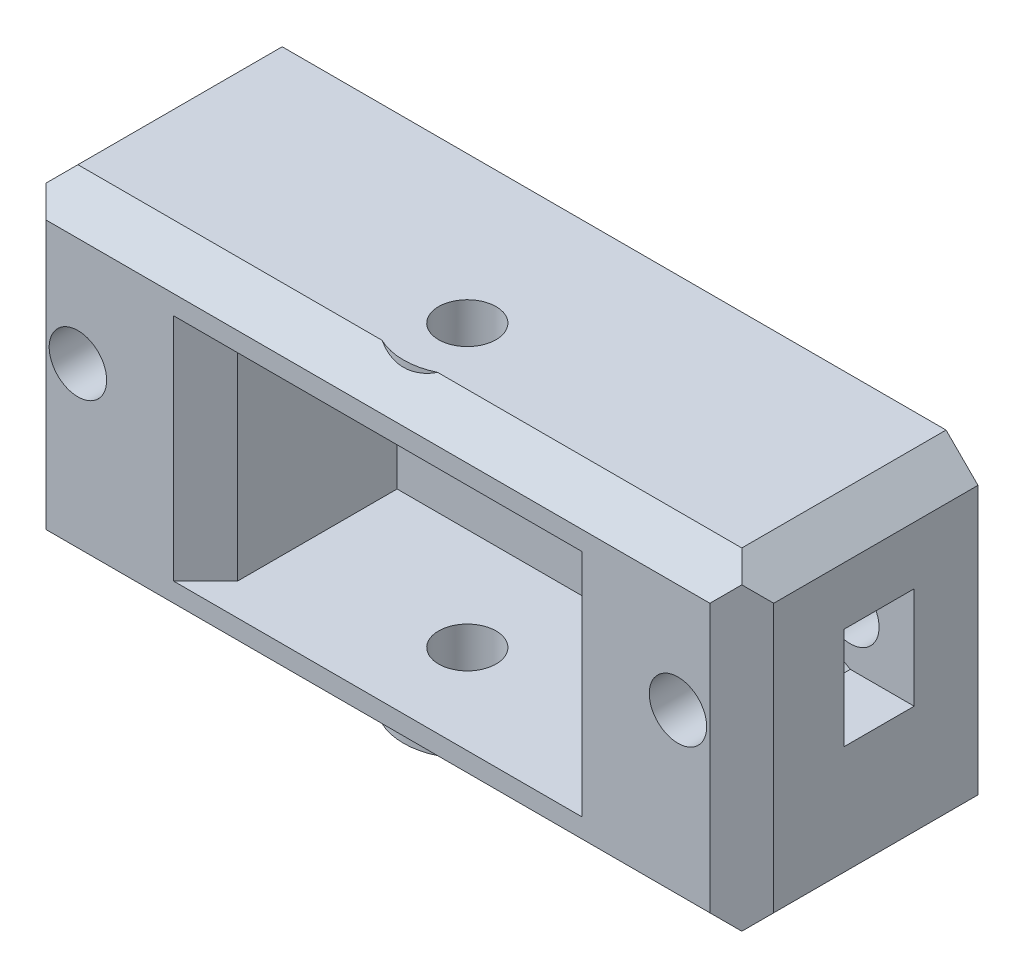
SolidWorks part; units mm, degrees
ref_plane "Plan de face" through (0, 0, 0) normal (0, 0, 1) x (1, 0, 0)
ref_plane "Plan de dessus" through (0, 0, 0) normal (0, 1, 0) x (1, 0, 0)
ref_plane "Plan de droite" through (0, 0, 0) normal (1, 0, 0) x (0, 0, -1)
sketch "Esquisse1" plane through (0, 0, 0) normal (0, 0, 1) x (1, 0, 0)
  line L1 (0, 0) -> (57, 0)
  line L2 (0, 0) -> (0, -26)
  line L3 (0, -26) -> (57, -26)
  line L4 (57, 0) -> (57, -26)
  line L5 (37.5, -6) -> (32, -6)
  line L6 (37.5, -6) -> (37.5, -16)
  line L7 (37.5, -16) -> (32, -16)
  line L8 (32, -6) -> (32, -16)
  line L9 (25, -6) -> (19.5, -6)
  line L10 (25, -6) -> (25, -16)
  line L11 (25, -16) -> (19.5, -16)
  line L12 (19.5, -6) -> (19.5, -16)
  circle A0 centre (5, -11) radius 2.25
  circle A1 centre (52, -11) radius 2.25
  point P17 (34.75, -6)
  point P18 (28.5, 0)
  dimension "D3" = 4.5
  dimension "D4" = 4.5
  dimension "D7" = 11
  dimension "D1" = 26
  dimension "D2" = 57
  dimension "D5" = 5
  dimension "D6" = 5
  dimension "D8" = 11
  dimension "D9" = 5.5
  dimension "D10" = 5.5
  dimension "D11" = 10
  dimension "D12" = 10
  dimension "D13" = 6
  dimension "D14" = 6
  dimension "D15" = 3.5
  dimension "D16" = 3.5
extrude "Boss.-Extru.2" add sketch "Esquisse1" along normal blind 3.5
ref_plane "Plan1" through (28.5, 0, 0) normal (1, 0, 0) x (0, 0, -1)
sketch "Esquisse6" plane through (0, 0, 3.5) normal (0, 0, 1) x (1, 0, 0)
  line L0 (15, 0) -> (15, -26)
  line L1 (57, 0) -> (0, 0) construction
  line L2 (0, -26) -> (57, -26) construction
  line L3 (15, -26) -> (42, -26)
  line L4 (42, -26) -> (42, 0)
  line L5 (42, 0) -> (57, 0)
  line L6 (57, 0) -> (57, -26)
  line L7 (57, -26) -> (42, -26)
  line L8 (15, -26) -> (0, -26)
  line L9 (0, -26) -> (0, 0)
  line L10 (0, 0) -> (15, 0)
  line L11 (15, -22) -> (42, -22)
  line L13 (0, 0) -> (57, 0)
  line L14 (0, 0) -> (0, -4)
  line L15 (0, -4) -> (57, -4)
  line L16 (57, 0) -> (57, -4)
  line L17 (0, -4) -> (57, -4)
  line L18 (0, -4) -> (0, 0)
  line L19 (0, 0) -> (57, 0)
  line L20 (57, -4) -> (57, 0)
  circle M9 centre (5, -11) radius 2.25
  line M10 (0, 0) -> (0, -26)
  line M11 (0, -26) -> (57, -26)
  line M12 (57, -26) -> (57, 0)
  line M13 (57, 0) -> (0, 0)
  circle M14 centre (52, -11) radius 2.25
  line M15 (32, -6) -> (37.5, -6)
  line M19 (19.5, -6) -> (25, -6)
  dimension "D1" = 15
  dimension "D2" = 15
  dimension "D3" = 4
  dimension "D4" = 18
  dimension "D5" = 4
  dimension "D6" = 26
extrude "Boss.-Extru.8" add sketch "Esquisse6" along normal blind 15 and the other way up to surface (3.5 mm away) contours L15 L9 L0 M11 M9 | L11 L0 L4 M11 | L15 L4 M11 M12 M14 | L4 L15 L6 M13 | L0 L15 L4 M19 M15 M13 | L15 L0 M10 M13 region at (28.5, -24, 3.5) region at (7.6266, -15.2025, 3.5) region at (7.5, -2, 3.5) region at (28.5, -2, 3.5) region at (49.3734, -15.2025, 3.5) region at (49.5, -2, 3.5) other way up to face at (34.75, -11, 0)
sketch "Esquisse7" plane through (0, 0, 0) normal (0, 1, 0) x (1, 0, 0)
  line L0 (15, -3.5) -> (42, -3.5) construction
  line L1 (28.5, -10.175) -> (28.5, 10.175) construction
  circle A0 centre (28.5, -11.5) radius 2.25
  point P4 (28.5, -3.5)
  dimension "D1" = 4.5
  dimension "D2" = 8
  dimension "D3" = 0
extrude "Enlèv. mat.-Extru.1" cut sketch "Esquisse7" against normal blind 30
sketch "Esquisse8" plane through (0, 0, 0) normal (0, 0, -1) x (-1, 0, 0)
  line L0 (-57, -26) -> (-57, 0) construction
  line L1 (-48.55, -12.9919) -> (-48.55, -9.0081)
  line L2 (-48.55, -9.0081) -> (-52, -7.0163)
  line L3 (-52, -7.0163) -> (-55.45, -9.0081)
  line L4 (-55.45, -9.0081) -> (-55.45, -12.9919)
  line L5 (-55.45, -12.9919) -> (-52, -14.9837)
  line L6 (-52, -14.9837) -> (-48.55, -12.9919)
  line L7 (-52, -7.0163) -> (-57, -7.0163)
  line L8 (-57, -7.0163) -> (-57, -14.9837)
  line L9 (-57, -14.9837) -> (-52, -14.9837)
  circle A0 centre (-52, -11) radius 3.45 construction
  line M7 (-57, 0) -> (-57, -26)
  circle M12 centre (-52, -11) radius 2.25
  dimension "D1" = 180
  dimension "D2" = 6.9
  dimension "D3" = 90
  dimension "D4" = 90
extrude "Enlèv. mat.-Extru.2" cut sketch "Esquisse8" against normal blind 5.5 from offset 5 contours L9 L5 L4 L3 L7 M7 | L5 L6 L1 L2 L3 L4 M12 region at (50.3277, -13.8965, 0) region at (55.5368, -11, 0) offset against normal yes
mirror "Symétrie1" about plane through (28.5, 0, 0) normal (1, 0, 0) of "Enlèv. mat.-Extru.2"
chamfer "Chanfrein2" distance 2.5 angle 45 2 edges at (57, -13, 18.5) (0, -13, 18.5)
chamfer "Chanfrein3" distance 2.5 angle 45 8 edges at (57, -26, 8) (57, 0, 8) (0, 0, 8) (0, -26, 8) (42, -13, 18.5) (15, -13, 18.5) (28.5, -26, 18.5) (28.5, 0, 18.5)
sketch "Esquisse10" plane through (0, 0, 0) normal (0, 1, 0) x (1, 0, 0)
  circle A0 centre (28.5, -11.5) radius 5
  circle A1 centre (28.5, -11.5) radius 2.75
  dimension "D1" = 10
extrude "Boss.-Extru.9" add sketch "Esquisse10" against normal up to next (4 mm away)
ref_plane "Plan2" through (0, -13, 0) normal (0, 1, 0) x (1, 0, 0)
mirror "Symétrie2" about plane through (0, -13, 0) normal (0, 1, 0) of "Boss.-Extru.9"
